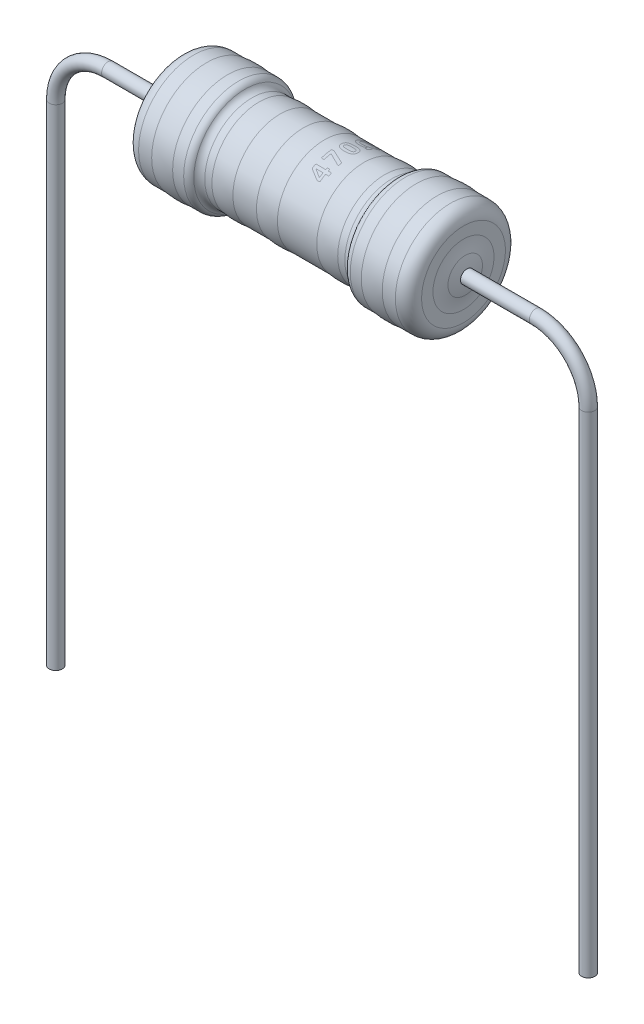
SolidWorks part; units mm, degrees
ref_plane "Front Plane" through (0, 0, 0) normal (0, 0, 1) x (1, 0, 0)
ref_plane "Top Plane" through (0, 0, 0) normal (0, 1, 0) x (1, 0, 0)
ref_plane "Right Plane" through (0, 0, 0) normal (1, 0, 0) x (0, 0, -1)
sketch "Sketch Set Wire Width" plane through (0, 0, 0) normal (0, 0, 1) x (1, 0, 0)
  line L0 (-8.16, 0) -> (8.16, 0)
  line L1 (-10.16, -2) -> (-10.16, -20.6984)
  line L2 (10.16, -2) -> (10.16, -20.6984)
  line L3 (-10.16, -20.6984) -> (10.16, -20.6984) construction
  line L4 (0, 0) -> (0, -20.6984) construction
  arc A0 (-8.16, 0) -> (-10.16, -2) centre (-8.16, -2) ccw
  arc A1 (8.16, 0) -> (10.16, -2) centre (8.16, -2) cw
  dimension "D2" = 2
  dimension "D3" = 60
  dimension "D1" = 20.32
sketch "Sketch Wire Diameter" plane through (0, 0, 0) normal (1, 0, 0) x (0, 0, -1)
  circle A0 centre (0, 0) radius 0.25
  dimension "D1" = 0.5
sweep "SET WIRE LENGTH" add profiles "Sketch Wire Diameter" path "Sketch Set Wire Width"
sketch "Sketch3" plane through (0, 0, 0) normal (0, 0, 1) x (1, 0, 0)
  line L0 (-5.4, 0) -> (5.4, 0)
  line L1 (0, 0) -> (0, 1.8) construction
  line L2 (-2.9, 1.8) -> (2.9, 1.8)
  line L3 (-5.4, 0) -> (-5.4, 1.6)
  line L4 (-4.9, 2.1) -> (-3.18, 2.1)
  line L5 (-2.9, 1.82) -> (-2.9, 1.8)
  line L6 (5.4, 0) -> (5.4, 1.6)
  line L7 (4.9, 2.1) -> (3.18, 2.1)
  line L8 (2.9, 1.82) -> (2.9, 1.8)
  arc A0 (-5.4, 1.6) -> (-4.9, 2.1) centre (-4.9, 1.6) cw
  arc A1 (5.4, 1.6) -> (4.9, 2.1) centre (4.9, 1.6) ccw
  arc A2 (-3.18, 2.1) -> (-2.9, 1.82) centre (-3.18, 1.82) cw
  arc A3 (3.18, 2.1) -> (2.9, 1.82) centre (3.18, 1.82) ccw
  dimension "D5" = 0.5
  dimension "D6" = 0.28
  dimension "D1" = 10.8
  dimension "D2" = 5.8
  dimension "D3" = 1.8
  dimension "D4" = 2.1
revolve "Revolve2" add sketch "Sketch3" angle 360 about L0
fillet "Fillet1" radius 0.3 2 edges at (2.9, 0, 1.8) (-2.9, 0, 1.8)
sketch "Sketch5" plane through (0, 0, 0) normal (0, 0, 1) x (1, 0, 0)
  line L0 (0, 0) -> (2, 0) construction
  line L1 (0, 0) -> (-0.3, 0) construction
  line L2 (-0.3, 0) -> (-2, 0) construction
  line L3 (-2, 0) -> (-4, 0) construction
  line L4 (2, 0) -> (4, 0) construction
  line L5 (-4, 0) -> (-4, 2.1) construction
  line L6 (-0.3, 0) -> (-0.3, 1.8) construction
  line L7 (-2, 0) -> (-2, 1.8) construction
  line L8 (2, 0) -> (2, 1.8) construction
  line L9 (4, 0) -> (4, 2.1) construction
  line L10 (-4, 2.1) -> (-4, 2.13) construction
  line L11 (-4.9, 2.1) -> (-3.18, 2.1) construction
  line L12 (4.9, 2.1) -> (3.18, 2.1) construction
  line L13 (-2.9, 1.8) -> (2.9, 1.8) construction
  line L14 (-2, 1.8) -> (-2, 1.83) construction
  line L17 (-4.4, 2.1) -> (-3.6, 2.1)
  line L19 (-5.4, 0) -> (5.4, 0) construction
  line L22 (-2.4, 1.8) -> (-1.6, 1.8) construction
  line L26 (-0.7, 1.8) -> (0.1, 1.8) construction
  line L30 (1.6, 1.8) -> (2.4, 1.8) construction
  line L34 (3.6, 2.1) -> (4.4, 2.1) construction
  line L36 (-0.3, 1.8) -> (-0.3, 1.83) construction
  line L37 (2, 1.8) -> (2, 1.83) construction
  line L38 (4, 2.1) -> (4, 2.13) construction
  arc A0 (-4.4, 2.1) -> (-3.6, 2.1) centre (-4, -0.5517) cw
  arc A1 (-2.4, 1.8) -> (-1.6, 1.8) centre (-2, -0.8517) cw construction
  arc A2 (-0.7, 1.8) -> (0.1, 1.8) centre (-0.3, -0.8517) cw construction
  arc A3 (1.6, 1.8) -> (2.4, 1.8) centre (2, -0.8517) cw construction
  arc A4 (3.6, 2.1) -> (4.4, 2.1) centre (4, -0.5517) cw construction
  dimension "D3" = 0.8
  dimension "D1" = 4
  dimension "D2" = 4
  dimension "D4" = 0.03
  dimension "D5" = 2
  dimension "D6" = 2
  dimension "D7" = 1.7
revolve "Band 1" add sketch "Sketch5" angle 360 about L2
sketch "Sketch8" plane through (0, 0, 0) normal (0, 0, 1) x (1, 0, 0)
  line L0 (-2.4, 1.8) -> (-1.6, 1.8) construction
  line L1 (-2.4, 1.8) -> (-1.6, 1.8)
  arc A0 (-1.6, 1.8) -> (-2.4, 1.8) centre (-2, -0.8517) ccw construction
  arc A1 (-1.6, 1.8) -> (-2.4, 1.8) centre (-2, -0.8517) ccw
revolve "Band 2" add sketch "Sketch8" angle 360 about L2
sketch "Sketch9" plane through (0, 0, 0) normal (0, 0, 1) x (1, 0, 0)
  line L0 (-0.7, 1.8) -> (0.1, 1.8) construction
  line L1 (-0.7, 1.8) -> (0.1, 1.8)
  arc A0 (0.1, 1.8) -> (-0.7, 1.8) centre (-0.3, -0.8517) ccw construction
  arc A1 (0.1, 1.8) -> (-0.7, 1.8) centre (-0.3, -0.8517) ccw
revolve "Band 3" add sketch "Sketch9" angle 360 about L2
sketch "Sketch10" plane through (0, 0, 0) normal (0, 0, 1) x (1, 0, 0)
  line L0 (1.6, 1.8) -> (2.4, 1.8) construction
  line L1 (1.6, 1.8) -> (2.4, 1.8)
  arc A0 (2.4, 1.8) -> (1.6, 1.8) centre (2, -0.8517) ccw construction
  arc A1 (2.4, 1.8) -> (1.6, 1.8) centre (2, -0.8517) ccw
revolve "Band 4" add sketch "Sketch10" angle 360 about L0
sketch "Sketch11" plane through (0, 0, 0) normal (0, 0, 1) x (1, 0, 0)
  line L0 (3.6, 2.1) -> (4.4, 2.1) construction
  line L1 (3.6, 2.1) -> (4.4, 2.1)
  arc A0 (4.4, 2.1) -> (3.6, 2.1) centre (4, -0.5517) ccw construction
  arc A1 (4.4, 2.1) -> (3.6, 2.1) centre (4, -0.5517) ccw
revolve "Band 5" add sketch "Sketch11" angle 360 about L4
sketch "Sketch12" plane through (0, 0, 0) normal (0, 0, 1) x (1, 0, 0)
  line L0 (-5.35, 0) -> (5.35, 0) construction
  line L1 (-5.35, 1) -> (-5.35, 0)
  line L2 (5.35, 1) -> (5.35, 0)
  line L3 (-5.35, 0) -> (-5.55, 0)
  line L4 (5.35, 0) -> (5.55, 0)
  arc A0 (-5.35, 1) -> (-5.55, 0) centre (-2.95, 0) ccw
  arc A1 (5.35, 1) -> (5.55, 0) centre (2.95, 0) cw
  dimension "D3" = 0.2
  dimension "D4" = 2.6
  dimension "D1" = 10.7
  dimension "D2" = 1
revolve "Revolve10" add sketch "Sketch12" angle 360 about L0
fillet "Fillet2" radius 2 2 edges at (5.4, 0, 0.8703) (-5.4, 0, -0.8703)
ref_plane "Plane2" through (0, 3, 0) normal (0, 1, 0) x (1, 0, 0)
sketch "Sketch13" plane through (0, 3, 0) normal (0, 1, 0) x (1, 0, 0)
  line L0 (0, 0) -> (1.15, 0) construction
  line L1 (1.15, 1.75) -> (1.15, -1.75) construction
  text T0 "470Ω" font "Calibri" height 0.6
  dimension "D1" = 3.5
  dimension "D2" = 1.15
wrap "Wrap1" sketch "Sketch13" wrap type scribe source sketch "Sketch13" face at (0.1, 1.8, 0)
